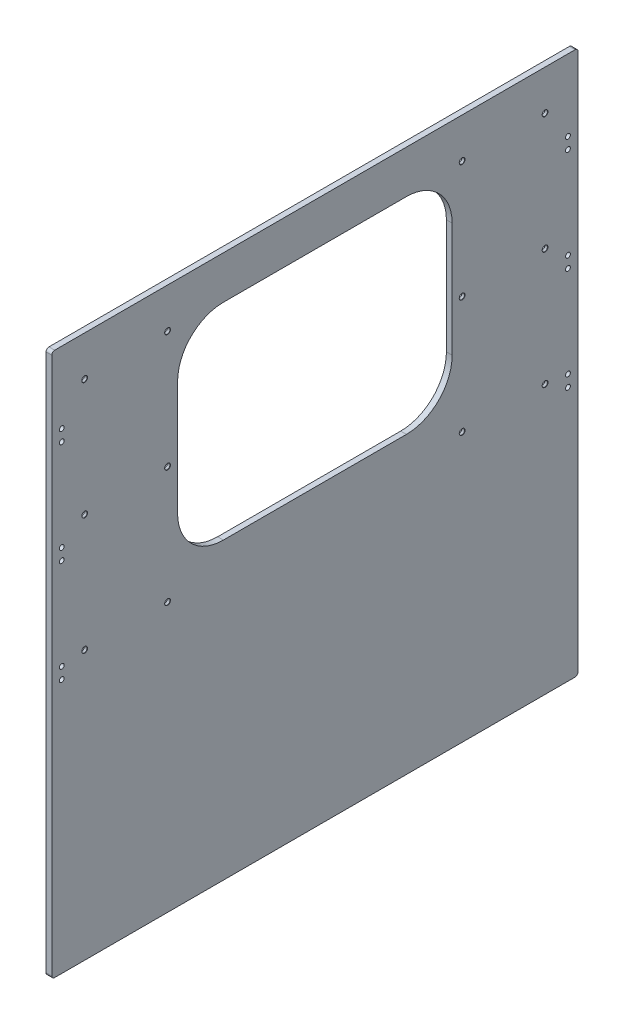
SolidWorks part; units mm, degrees
material "PE High Density"
ref_plane "Front Plane" through (0, 0, 0) normal (0, 0, 1) x (1, 0, 0)
ref_plane "Top Plane" through (0, 0, 0) normal (0, 1, 0) x (1, 0, 0)
ref_plane "Right Plane" through (0, 0, 0) normal (1, 0, 0) x (0, 0, -1)
sketch "Sketch1" plane through (0, 0, 0) normal (1, 0, 0) x (0, 0, -1)
  line L0 (6.35, 0) -> (1162.05, 0)
  line L1 (0, 6.35) -> (0, 1200.15)
  line L2 (1168.4, 6.35) -> (1168.4, 1200.15)
  line L3 (6.35, 1206.5) -> (1162.05, 1206.5)
  line L4 (381, 1111.25) -> (787.4, 1111.25)
  line L5 (279.4, 1009.65) -> (279.4, 755.65)
  line L6 (889, 1009.65) -> (889, 755.65)
  line L7 (381, 654.05) -> (787.4, 654.05)
  line L8 (279.4, 755.65) -> (0, 755.65) construction
  line L9 (889, 755.65) -> (1168.4, 755.65) construction
  arc A0 (0, 6.35) -> (6.35, 0) centre (6.35, 6.35) ccw
  arc A1 (1162.05, 0) -> (1168.4, 6.35) centre (1162.05, 6.35) ccw
  arc A2 (1168.4, 1200.15) -> (1162.05, 1206.5) centre (1162.05, 1200.15) ccw
  arc A3 (6.35, 1206.5) -> (0, 1200.15) centre (6.35, 1200.15) ccw
  arc A4 (279.4, 755.65) -> (381, 654.05) centre (381, 755.65) ccw
  arc A5 (889, 755.65) -> (787.4, 654.05) centre (787.4, 755.65) cw
  arc A6 (787.4, 1111.25) -> (889, 1009.65) centre (787.4, 1009.65) cw
  arc A7 (279.4, 1009.65) -> (381, 1111.25) centre (381, 1009.65) cw
  point P11 (0, 0)
  point P14 (1168.4, 0)
  point P17 (1168.4, 1206.5)
  point P20 (0, 1206.5)
  point P23 (279.4, 654.05)
  point P28 (889, 1111.25)
  point P31 (279.4, 1111.25)
  dimension "D7" = 6.35
  dimension "D8" = 101.6
  dimension "D1" = 1168.4
  dimension "D2" = 609.6
  dimension "D4" = 1206.5
  dimension "D5" = 654.05
  dimension "D6" = 457.2
extrude "Boss-Extrude1" add sketch "Sketch1" along normal blind 12.7
hole_wizard "CSK for 1/4 Flat Head Machine Screw1" positions "Sketch2" profile "Sketch3" countersink size "1/4" standard "ANSI Inch" end condition through all
sketch "Sketch2" plane through (12.7, 0, 0) normal (1, 0, 0) x (0, 0, -1)
  line L3 (1162.05, 1206.5) -> (6.35, 1206.5) construction
  line L4 (279.4, 1009.65) -> (279.4, 755.65) construction
  line L5 (889, 755.65) -> (889, 1009.65) construction
  point P0 (73.025, 1117.6)
  point P2 (73.025, 857.25)
  point P4 (73.025, 596.9)
  point P6 (257.175, 1117.6)
  point P8 (257.175, 857.25)
  point P10 (257.175, 596.9)
  point P12 (911.225, 1117.6)
  point P14 (911.225, 857.25)
  point P16 (911.225, 596.9)
  point P18 (1095.375, 1117.6)
  point P20 (1095.375, 857.25)
  point P22 (1095.375, 596.9)
  dimension "D1" = 184.15
  dimension "D2" = 184.15
  dimension "D3" = 22.225
  dimension "D4" = 22.225
  dimension "D5" = 88.9
  dimension "D6" = 260.35
  dimension "D7" = 260.35
sketch "Sketch3" plane through (12.7, 1117.6, -73.025) normal (0, 1, 0) x (0, 0, -1)
  line L0 (0, 0) -> (0, 12.7)
  line L1 (0, 12.7) -> (3.3782, 12.7)
  line L2 (3.3782, 12.7) -> (3.3782, 4.5369)
  line L3 (3.3782, 4.5369) -> (6.4389, 1.016)
  line L4 (6.4389, 1.016) -> (6.4389, 0)
  line L6 (6.4389, 0) -> (0, 0)
  line L7 (-3.3782, 4.5369) -> (-6.4389, 1.016) construction
  line L11 (0, -6.35) -> (0, 107.95) construction
  dimension "Thru Hole Dia." = 6.7564
  dimension "Thru Hole Depth" = 12.7
  dimension "C'Sink Dia." = 12.8778
  dimension "C'Sink Angle" = 82
  dimension "Head Clearance" = 1.016
hole_wizard "27/64 (0.42188) Diameter Hole1" positions "Sketch4" profile "Sketch5" hole size "27/64" standard "ANSI Inch" end condition through all
sketch "Sketch4" plane through (12.7, 0, 0) normal (1, 0, 0) x (0, 0, -1)
  line L0 (0, 1200.15) -> (0, 6.35) construction
  line L1 (1168.4, 6.35) -> (1168.4, 1200.15) construction
  line L2 (1162.05, 1206.5) -> (6.35, 1206.5) construction
  point P0 (22.225, 1047.75)
  point P2 (22.225, 1022.35)
  point P4 (22.225, 819.15)
  point P6 (22.225, 793.75)
  point P8 (22.225, 590.55)
  point P10 (22.225, 565.15)
  point P12 (1146.175, 1047.75)
  point P14 (1146.175, 1022.35)
  point P16 (1146.175, 819.15)
  point P18 (1146.175, 793.75)
  point P20 (1146.175, 565.15)
  point P22 (1146.175, 590.55)
  dimension "D1" = 22.225
  dimension "D2" = 22.225
  dimension "D3" = 25.4
  dimension "D4" = 25.4
  dimension "D5" = 25.4
  dimension "D6" = 228.6
  dimension "D7" = 228.6
  dimension "D8" = 158.75
sketch "Sketch5" plane through (12.7, 1047.75, -22.225) normal (0, 1, 0) x (0, 0, -1)
  line L0 (0, 0) -> (0, 12.7)
  line L1 (0, 12.7) -> (5.3579, 12.7)
  line L2 (5.3579, 12.7) -> (5.3579, 0)
  line L5 (5.3579, 0) -> (0, 0)
  line L11 (0, -6.35) -> (0, 107.95) construction
  dimension "Thru Hole Dia." = 10.7158
  dimension "Thru Hole Depth" = 12.7
